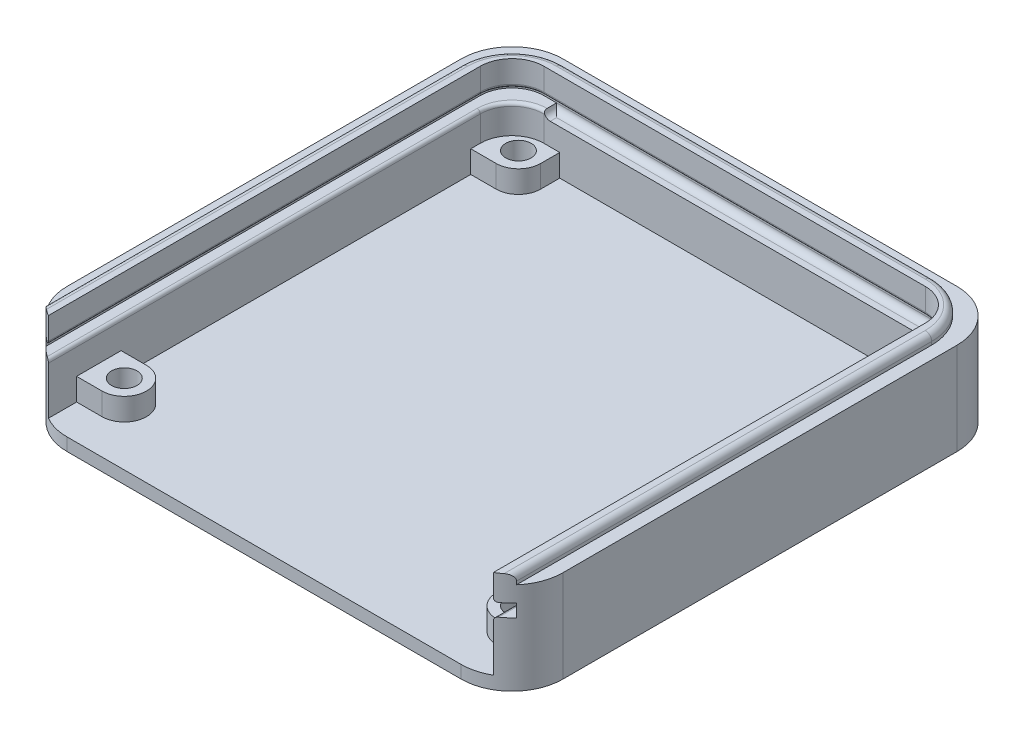
SolidWorks part; units mm, degrees
ref_plane "Plano frontal" through (0, 0, 0) normal (0, 0, 1) x (1, 0, 0)
ref_plane "Plano superior" through (0, 0, 0) normal (0, 1, 0) x (1, 0, 0)
ref_plane "Plano direito" through (0, 0, 0) normal (1, 0, 0) x (0, 0, -1)
sketch "Sketch2" plane through (0, 0, 0) normal (0, 1, 0) x (1, 0, 0)
  line L0 (-76, 0) -> (-76, 76)
  line L1 (0, 0) -> (-78, 0)
  line L2 (0, 0) -> (0, 78)
  line L3 (0, 78) -> (-78, 78)
  line L4 (-78, 0) -> (-78, 78)
  line L5 (-76, 76) -> (-2, 76)
  line L6 (-2, 76) -> (-2, 0)
  dimension "D1" = 78
  dimension "D2" = 78
  dimension "D3" = 2
  dimension "D4" = 2
  dimension "D5" = 2
extrude "Boss-Extrude1" add sketch "Sketch2" along normal blind 16 contours L5 L6 L1 L2 L3 L4 L0 region at (-77, 0, -1.1031)
extrude "Boss-Extrude2" add sketch "Sketch2<4>" along normal blind 2 contours L6 L5 L0 L1 region at (-39, 0, -38)
sketch "Sketch2<4>" plane through (0, 0, 0) normal (0, 1, 0) x (1, 0, 0) same geometry as "Sketch2"
sketch "Sketch3" plane through (0, 0, 0) normal (0, 0, 1) x (1, 0, 0)
  line L0 (-76, 16) -> (-74, 16)
  line L1 (-76, 16) -> (-78, 16) construction
  line L2 (-74, 16) -> (-74, 12)
  line L3 (-74, 12) -> (-76, 12)
  line L4 (-76, 12) -> (-76, 16)
  line L5 (-76, 16) -> (-76, 2) construction
  line L6 (-76, 10) -> (-74, 10)
  line L7 (-74, 10) -> (-74, 2)
  line L8 (-2, 2) -> (-76, 2) construction
  line L9 (-76, 10) -> (-76, 2)
  line L10 (-76, 2) -> (-74, 2)
  dimension "D1" = 0
  dimension "D2" = 8
  dimension "D3" = 2
  dimension "D4" = 2
  dimension "D5" = 2
extrude "Boss-Extrude3" add sketch "Sketch3" against normal blind 76 contours L4 L0 L2 L3 | L10 L7 L6 L9
pattern_linear "LPattern1" count 2 spacing 72 along (1, 0, 0) of "Boss-Extrude3"
sketch "Sketch4" plane through (-74, 0, 0) normal (1, 0, 0) x (0, 0, -1)
  line L0 (76, 16) -> (76, 12) construction
  line L1 (76, 16) -> (74, 16)
  line L2 (76, 16) -> (76, 12)
  line L3 (76, 12) -> (74, 12)
  line L4 (74, 16) -> (74, 12)
  line L5 (76, 16) -> (0, 16) construction
  line L6 (76, 12) -> (0, 12) construction
  line L8 (76, 10) -> (74, 10)
  line L9 (76, 10) -> (76, 2)
  line L10 (76, 2) -> (74, 2)
  line L11 (74, 10) -> (74, 2)
  line L12 (76, 2) -> (0, 2) construction
  dimension "D1" = 2
  dimension "D2" = 2
extrude "Boss-Extrude5" add sketch "Sketch4" along normal blind 71
fillet "Fillet2" radius 5 6 edges at (-2, 11, -76) (-4, 14, -74) (-4, 6, -74) (-74, 6, -74) (-74, 14, -74) (-76, 11, -76)
sketch "Sketch7" plane through (0, 2, 0) normal (0, 1, 0) x (1, 0, 0)
  line L0 (-66.5, 71) -> (-66.5, 74)
  line L1 (-9, 74) -> (-69, 74) construction
  line L2 (-74, 74.4911) -> (-66.5, 74.4911)
  line L3 (-70, 67.5) -> (-74, 67.5)
  line L4 (-74, 69) -> (-74, 0) construction
  line L5 (-74, 67.5) -> (-74, 74.4911)
  line L6 (-11.5, 71) -> (-11.5, 74.5)
  line L7 (-66.5, 74.4911) -> (-66.5, 71)
  line L8 (-11.5, 74.5) -> (-4, 74.5)
  line L9 (-8, 67.5) -> (-4, 67.5)
  line L10 (-4, 69) -> (-4, 0) construction
  line L11 (-4, 67.5) -> (-4, 74.5)
  line L12 (-70, 5.5) -> (-74, 5.5)
  line L13 (-74, 69) -> (-74, 0) construction
  line L14 (-74, 5.5) -> (-74, 12.5)
  line L15 (-74, 12.5) -> (-70, 12.5)
  line L16 (-8, 12.5) -> (-4, 12.5)
  line L17 (-4, 69) -> (-4, 0) construction
  line L18 (-4, 12.5) -> (-4, 5.5)
  line L19 (-4, 5.5) -> (-8, 5.5)
  circle A8 centre (-70, 71) radius 2
  circle A9 centre (-70, 71) radius 3.5
  circle A10 centre (-8, 71) radius 2
  circle A11 centre (-8, 71) radius 3.5
  circle A12 centre (-8, 9) radius 2
  circle A13 centre (-8, 9) radius 3.5
  circle A14 centre (-70, 9) radius 2
  circle A15 centre (-70, 9) radius 3.5
  point P6 (-70.25, 74.4911)
  line M1 (-4, 0) -> (-4, 69)
  line M3 (-74, 69) -> (-74, 0)
  arc M6 (-4, 69) -> (-9, 74) centre (-9, 69) ccw
  line M7 (-9, 74) -> (-69, 74)
  arc M8 (-69, 74) -> (-74, 69) centre (-69, 69) ccw
  dimension "D1" = 4
  dimension "D2" = 7
  dimension "D3" = 71
  dimension "D4" = 70
  dimension "D5" = 62
  dimension "D6" = 62
extrude "Boss-Extrude9" add sketch "Sketch7" along normal blind 3.5 contours A9 L3 M8 M3 | A9 L0 M7 | A11 L9 M1 M6 | A11 L6 M7 | A11 A10 M6 M7 | A13 A12 | A13 L19 L16 M1 | A15 L15 L12 M3 | A15 A14 | A9 | A8 region at (-66.9777, 2, -73.2911) region at (-72, 2, -12.4194) region at (-4.0806, 2, -9) region at (-11.0223, 2, -73.2911) region at (-73.0818, 2, -68.5513) region at (-10.9631, 2, -72.6764) region at (-4.9182, 2, -68.5513) region at (-67.5951, 2, -11.4049) region at (-5.5951, 2, -11.4049)
sketch "Sketch8" plane through (0, 0, -74) normal (0, 0, 1) x (1, 0, 0)
  line L0 (-9, 10) -> (-69, 10) construction
  line L1 (-69, 10) -> (-9, 10)
  line L2 (-69, 10) -> (-69, 9)
  line L3 (-69, 9) -> (-9, 9)
  line L4 (-9, 10) -> (-9, 9)
  line L5 (-9, 5.5) -> (-9, 10) construction
  line L6 (-69, 10) -> (-69, 5.5) construction
  dimension "D1" = 1
extrude "Cut-Extrude1" cut sketch "Sketch8" against normal blind 2
fillet "Fillet12" radius 1 3 edges at (-9, 9, -75) (-69, 9, -75) (-39, 9, -76)
sketch "Sketch11" plane through (0, 0, 0) normal (0, 0, 1) x (1, 0, 0)
  line L1 (-78, 16) -> (-76, 16)
  line L2 (-78, 16) -> (-78, 14.5)
  line L3 (-78, 14.5) -> (-76, 14.5)
  line L4 (-76, 16) -> (-76, 14.5)
  line L5 (0, 16) -> (-2, 16)
  line L6 (0, 16) -> (0, 14.5)
  line L7 (0, 14.5) -> (-2, 14.5)
  line L8 (-2, 16) -> (-2, 14.5)
  dimension "D1" = 1.5
  dimension "D2" = 2
  dimension "D3" = 1.5
  dimension "D4" = 2
extrude "Cut-Extrude2" cut sketch "Sketch11" against normal through all
sketch "Sketch12" plane through (-76, 0, 0) normal (-1, 0, 0) x (0, 0, 1)
  line L0 (-78, 14.5) -> (0, 14.5) construction
  line L1 (-78, 16) -> (-76, 16)
  line L2 (-78, 16) -> (-78, 14.5)
  line L3 (-78, 14.5) -> (-76, 14.5)
  line L4 (-76, 16) -> (-76, 14.5)
  dimension "D1" = 2
extrude "Cut-Extrude3" cut sketch "Sketch12" against normal through all
fillet "Fillet13" radius 8 6 edges at (-78, 7.25, -78) (-76, 15.25, -76) (0, 7.25, -78) (-2, 15.25, -76) (0, 7.25, 0) (-78, 7.25, 0)
fillet "Fillet14" radius 1 5 edges at (-2, 16, -35.3542) (-4.3431, 16, -73.6569) (-39, 16, -76) (-73.6569, 16, -73.6569) (-76, 16, -35.3542)
fillet "Fillet16" radius 0.5 9 edges at (-4, 12, -35.0359) (-5.4645, 12, -72.5355) (-39, 12, -74) (-72.5355, 12, -72.5355) (-74, 12, -35.0359) (-5.4645, 10, -72.5355) (-72.5355, 10, -72.5355) (-4, 10, -35.0359) (-74, 10, -35.0359)
